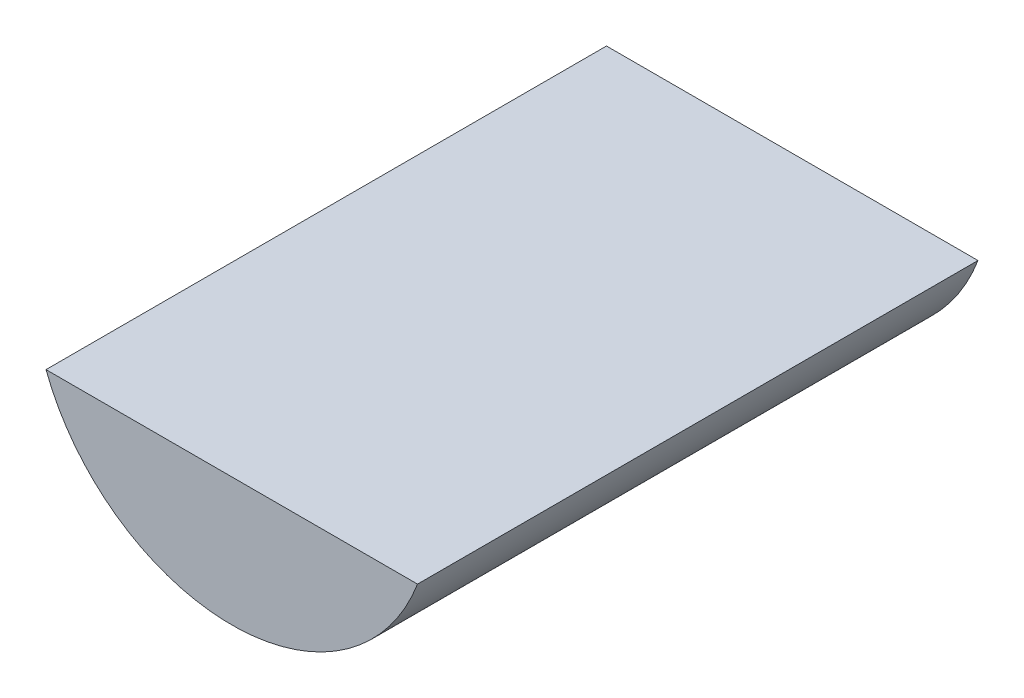
SolidWorks part; units mm, degrees
ref_plane "Front Plane" through (0, 0, 0) normal (0, 0, 1) x (1, 0, 0)
ref_plane "Top Plane" through (0, 0, 0) normal (0, 1, 0) x (1, 0, 0)
ref_plane "Right Plane" through (0, 0, 0) normal (1, 0, 0) x (0, 0, -1)
sketch "Sketch1" plane through (0, 0, 0) normal (0, -1, 0) x (1, 0, 0)
  line L26 (-5222.2849, -22482.2125) -> (-5222.2849, -23836.1382)
  line L27 (0, -20936.6209) -> (-5222.2849, -23836.1382)
  line L28 (-2192.0702, -19340.7843) -> (-2192.0702, -20044.0138) construction
  line L29 (-2192.0702, -20044.0138) -> (-2192.0702, -22153.7022) construction
  line L30 (0, -18035.3515) -> (-5222.2849, -22820.6939) construction
  line L31 (0, -17068.2617) -> (0, -20936.6209)
  line L32 (-5222.2849, -22482.2125) -> (0, -17068.2617)
  line L33 (6330.1244, -18035.3515) -> (-6330.1244, -18035.3515) construction
  line L34 (8.74, -7690.9257) -> (-20379.8424, -7690.9257) construction
  line L35 (-9571.2788, 936.469) -> (-6739.1788, 936.469)
  line L36 (-9571.2788, 7879.559) -> (-6739.1788, 7879.559)
  line L37 (-8155.2288, 7879.559) -> (-8155.2288, 936.469) construction
  line L38 (-9571.2788, 936.469) -> (-9571.2788, 7879.559)
  line L39 (-6739.1788, 936.469) -> (-6739.1788, 7879.559)
  line L40 (-15240, -2306.2961) -> (0, 9388.0859)
  line L41 (0, 9388.0721) -> (-20379.8424, -6249.931) construction
  line L42 (0, 7877.8019) -> (-15240, -3082.1645) construction
  line L43 (-8554.5017, 3821.9095) -> (-8554.5017, 2823.972)
  line L44 (-8554.5017, 2823.972) -> (-8554.5017, -169.8406)
  line L45 (-8554.5017, 2823.972) -> (8554.5017, 2823.972) construction
  line L46 (-15240, -2306.2961) -> (-15240, -3858.0329)
  line L47 (0, 10760.4479) -> (0, 5270.9444)
  line L48 (-15240, -3858.0329) -> (0, 6367.5179)
  line L49 (-20379.8424, -5769.5995) -> (-20379.8424, -7690.9257)
  line L50 (-20379.8424, -7690.9257) -> (0, 5270.9444)
  line L51 (0, 10760.4479) -> (-20379.8424, -5769.5995)
  line L53 (5222.2849, -22482.2125) -> (5222.2849, -23836.1382)
  line L54 (0, -20936.6209) -> (5222.2849, -23836.1382)
  line L55 (2192.0702, -19340.7843) -> (2192.0702, -20044.0138) construction
  line L56 (2192.0702, -20044.0138) -> (2192.0702, -22153.7022) construction
  line L57 (0, -18035.3515) -> (5222.2849, -22820.6939) construction
  line L58 (5222.2849, -22482.2125) -> (0, -17068.2617)
  line L59 (8155.2288, 7879.559) -> (8155.2288, 936.469) construction
  line L60 (-8.74, -7690.9257) -> (20379.8424, -7690.9257) construction
  line L61 (20379.8424, -5769.5995) -> (20379.8424, -7690.9257)
  line L62 (20379.8424, -7690.9257) -> (0, 5270.9444)
  line L63 (0, 9388.0721) -> (20379.8424, -6249.931) construction
  line L64 (8554.5017, 3821.9095) -> (8554.5017, 2823.972)
  line L65 (8554.5017, 2823.972) -> (8554.5017, -169.8406)
  line L66 (0, 7877.8019) -> (15240, -3082.1645) construction
  line L67 (15240, -2306.2961) -> (15240, -3858.0329)
  line L68 (15240, -3858.0329) -> (0, 6367.5179)
  line L69 (15240, -2306.2961) -> (0, 9388.0859)
  line L70 (9571.2788, 936.469) -> (6739.1788, 936.469)
  line L71 (6739.1788, 936.469) -> (6739.1788, 7879.559)
  line L72 (9571.2788, 7879.559) -> (6739.1788, 7879.559)
  line L73 (9571.2788, 936.469) -> (9571.2788, 7879.559)
  line L74 (0, 10760.4479) -> (20379.8424, -5769.5995)
  point P0 (-8155.2288, 5102.2214)
  point P2 (-4907.0215, 4348.8786)
  point P4 (-8554.5017, 3821.9095)
  point P61 (8155.2288, 5102.2214)
sketch "Sketch2" plane through (0, 0, 0) normal (0, 1, 0) x (1, 0, 0)
  line L2 (2260.3073, 18179.796) -> (2260.3073, -14205.204)
  line L3 (2260.3073, -14205.204) -> (-1702.0927, -14205.204)
  line L4 (-1702.0927, 18179.796) -> (-1702.0927, -14205.204)
  arc A1 (2260.3073, 18179.796) -> (-1702.0927, 18179.796) centre (279.1073, 18179.796) ccw
ref_plane "Plane1" through (0, 0, -4572) normal (0, 0, 1) x (1, 0, 0)
sketch "Sketch3" plane through (0, 0, -4572) normal (0, 0, 1) x (1, 0, 0)
  line L0 (-1193.8, -762) -> (1193.8, -762)
  line L1 (1193.8, -762) -> (1193.8, -1384.3)
  line L2 (1193.8, -1384.3) -> (577.85, -1790.7)
  line L3 (577.85, -1790.7) -> (-577.85, -1790.7)
  line L4 (-577.85, -1790.7) -> (-1193.8, -1384.3)
  line L5 (-1193.8, -1384.3) -> (-1193.8, -762)
  line L6 (0, -762) -> (0, -1790.7) construction
  line L7 (1809.9064, -685.8) -> (-1809.9064, -685.8)
  line L8 (-1365.5754, 1371.6) -> (1365.5754, 1371.6)
  line L9 (524.5046, 1371.6) -> (609.6, 889)
  line L10 (609.6, 889) -> (1719.2329, 889)
  line L12 (-524.5046, 1371.6) -> (-609.6, 889)
  line L13 (-609.6, 889) -> (-1719.2329, 889)
  line L14 (-1935.48, 0) -> (1935.48, 0)
  circle A0 centre (0, 0) radius 1935.48
  point P15 (0, 1935.48)
  dimension "D1" = 3870.96
  dimension "D7" = 2057.4
  dimension "D2" = 1155.7
  dimension "D3" = 2387.6
  dimension "D4" = 622.3
  dimension "D5" = 1028.7
  dimension "D6" = 762
  dimension "D8" = 76.2
  dimension "D9" = 1574.8
  dimension "D10" = 609.6
  dimension "D11" = 100
  dimension "D12" = 2387.6
extrude "Boss-Extrude1" add sketch "Sketch3" against normal blind 1092.2 contours L7 A0 L4 L5 L0 L1 L2 L3 region at (0, -1897.1854, -4572)
extrude "Boss-Extrude2" add sketch "Sketch3<4>" against normal blind 17.78 contours L7 A0 L4 L5 L0 L1 L2 L3 | L6 L0 L5 L4 L3 | L0 L6 L3 L2 L1 region at (-552.4618, -1233.353, -4572) region at (552.4618, -1233.353, -4572) region at (0, -1897.1854, -4572)
sketch "Sketch3<4>" plane through (0, 0, -4572) normal (0, 0, 1) x (1, 0, 0) same geometry as "Sketch3"
pattern_linear "LPattern1" count 5 spacing 1092.2 along (0, 0, -1) of "Boss-Extrude1", "Boss-Extrude2"
sketch "Sketch4" plane through (0, -685.8, 0) normal (0, 1, 0) x (1, 0, 0)
  line L0 (0, 4572) -> (0, 10033) construction
  line L3 (-1809.9064, 10033) -> (1809.9064, 10033) construction
  line L8 (1809.9064, 4572) -> (-1809.9064, 4572) construction
  point P2 (0, 2711.0587)
  point P3 (0, 0)
  point P4 (0, 0)
  point P6 (0, 7302.5)
  point P8 (0, 0)
  point P11 (0, 0)
  point P13 (0, 0)
  point P14 (0, 0)
  point P16 (0, 0)
  dimension "D1" = 10126.472
move or copy body "Body-Move/Copy1" bodies to move or copy 103 copy no translate (0, 76.2, 0)
